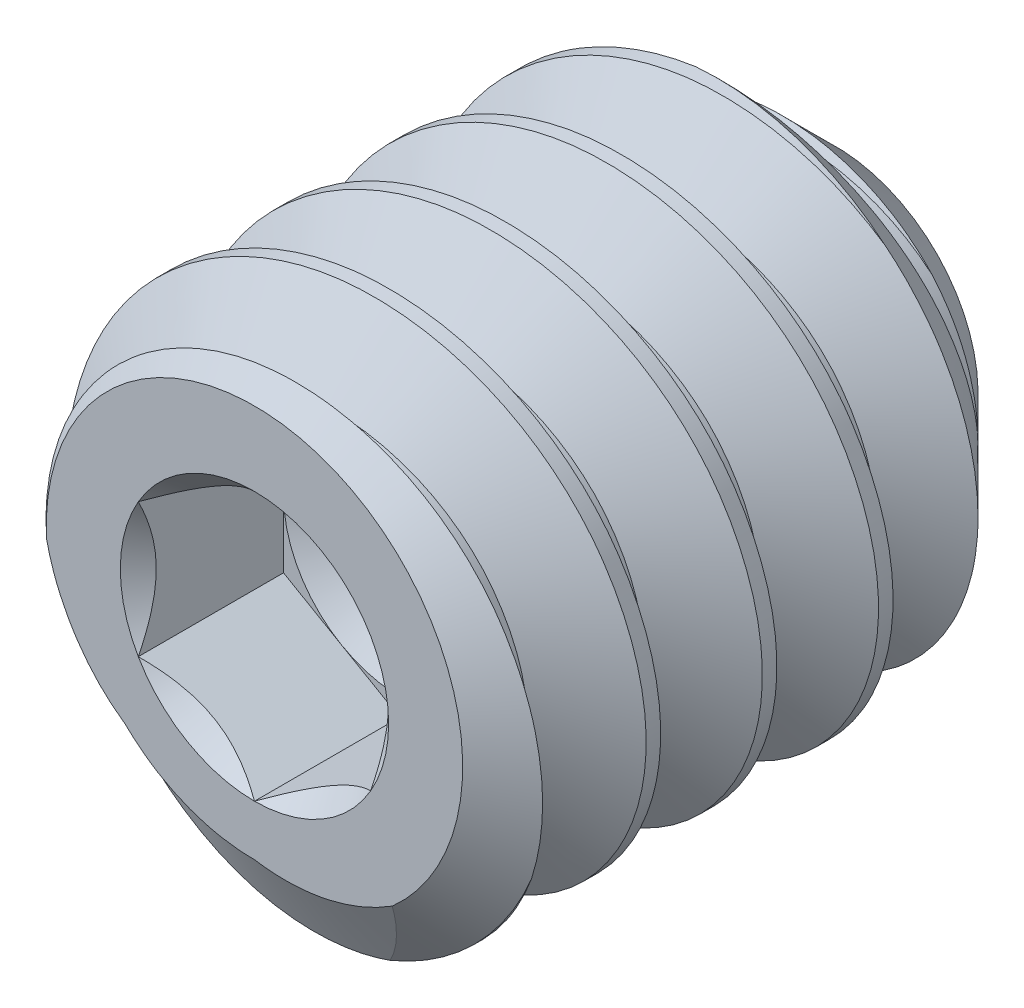
SolidWorks part; units mm, degrees
ref_plane "Front" through (0, 0, 0) normal (0, 0, 1) x (1, 0, 0)
ref_plane "Top" through (0, 0, 0) normal (0, 1, 0) x (1, 0, 0)
ref_plane "Right" through (0, 0, 0) normal (1, 0, 0) x (0, 0, -1)
sketch "Sketch22" plane through (0, 0, 0) normal (1, 0, 0) x (0, 0, -1)
  line L0 (-1.3533, 0) -> (-1.3533, 1.1379)
  line L1 (-1.3533, 1.1379) -> (-1.1541, 1.4224)
  line L2 (-1.1541, 1.4224) -> (1.1787, 1.4224)
  line L3 (1.1787, 1.4224) -> (1.8217, 0.7794)
  line L4 (1.8217, 0.7794) -> (1.3533, 0) construction
  line L5 (1.3533, 0) -> (-1.3533, 0)
  line L6 (1.3533, 0) -> (1.8217, 0) construction
  line L7 (1.8217, 0) -> (1.8217, 0.7794) construction
  line L8 (1.8217, -0.7794) -> (1.3533, 0) construction
  line L9 (-1.1541, -1.4224) -> (1.1787, -1.4224) construction
  line L10 (1.8217, 0.7794) -> (1.8217, 0)
  line L11 (1.8217, 0) -> (1.3533, 0)
  dimension "Dia" = 2.8448
  dimension "Length" = 3.175
  dimension "D3" = 35
  dimension "D5" = 118
  dimension "D6" = 45
  dimension "D7" = 2.2758
revolve "Revolve1" add sketch "Sketch22" angle 360 about L6
ref_plane "Plane1" through (0, 0, -1.8217) normal (0, 0, 1) x (1, 0, 0)
sketch "Sketch27" plane through (0, 0, -1.8217) normal (0, 0, 1) x (1, 0, 0)
  circle A0 centre (0, 0) radius 1.4224 construction
  circle A1 centre (0, 0) radius 1.4224
curve "Helix/Spiral1" pitch 0.635 height 3.81 radius 1.4224 centre (0, 0, -1.8217) axis (0, 0, 1) start towards (0, 1, 0)
sketch "Sketch28" plane through (0, 0, 0) normal (1, 0, 0) x (0, 0, -1)
  line L0 (1.8217, 1.4224) -> (2.3773, 1.4224)
  line L1 (2.3773, 1.4224) -> (2.1392, 1.01)
  line L2 (2.1392, 1.01) -> (2.0598, 1.01)
  line L3 (2.0598, 1.01) -> (1.8217, 1.4224)
  line L4 (1.9407, 1.2162) -> (2.2582, 1.2162) construction
  line L6 (-1.1541, 1.4224) -> (1.1787, 1.4224) construction
  line L7 (1.8217, 6.985) -> (1.8217, -6.985) construction
  dimension "D1" = 0.0794
  dimension "D2" = 0.3175
  dimension "D3" = 60
sweep "Cut-Sweep2" cut profiles "Sketch28" path "Helix/Spiral1" align with end faces yes
sketch "Sketch23" plane through (0, 0, 1.3533) normal (0, 0, 1) x (1, 0, 0)
  line L1 (0, 0.7332) -> (-0.635, 0.3666)
  line L2 (-0.635, 0.3666) -> (-0.635, -0.3666)
  line L3 (-0.635, -0.3666) -> (0, -0.7332)
  line L4 (0, -0.7332) -> (0.635, -0.3666)
  line L5 (0.635, -0.3666) -> (0.635, 0.3666)
  line L6 (0.635, 0.3666) -> (0, 0.7332)
  circle A0 centre (0, 0) radius 0.635 construction
  dimension "Hex" = 1.27
extrude "Cut-Extrude10" cut sketch "Sketch23" against normal blind 0.7937
sketch "Sketch24" plane through (0, 0, 1.3533) normal (0, 0, 1) x (1, 0, 0)
  circle A0 centre (0, 0) radius 0.7332
extrude "Cut-Extrude11" cut sketch "Sketch24" against normal through all draft 45
sketch "Sketch26" plane through (0, 0, 0.5596) normal (0, 0, 1) x (1, 0, 0)
  circle A0 centre (0, 0) radius 0.635 construction
  circle A1 centre (0, 0) radius 0.635
extrude "Cut-Extrude12" cut sketch "Sketch26" against normal through all draft 60
sketch "Sketch30" plane through (0, 0, 0) normal (1, 0, 0) x (0, 0, -1)
  line L0 (-1.1541, 1.4224) -> (1.1787, 1.4224) construction
  line L1 (-1.3533, 0) -> (-1.3533, 1.1379) construction
  line L2 (1.8217, 0) -> (1.8217, 0.7794) construction
  line L3 (-1.1541, -1.4224) -> (1.1787, -1.4224) construction
  point P0 (-1.3533, 1.4224)
  point P1 (1.8217, 1.4224)
  point P2 (1.8217, -1.4224)
  point P11 (-0.4008, -1.4224)
  dimension "D1" = 2.2225
sketch "Sketch31" plane through (0, 0, 0) normal (1, 0, 0) x (0, 0, -1)
  line L2 (1.3533, 0) -> (1.8217, -0.7794)
  line L3 (1.8217, 0.7794) -> (1.3533, 0)
equation "\"D7@Sketch22\"=\"Dia@Sketch22\"*.8"
equation "\"D1@Sketch28\" = \"D4@Helix/Spiral1\" * .125"
equation "\"D3@Helix/Spiral1\" = \"Length@Sketch22\" + \"D4@Helix/Spiral1\""
equation "\"D1@Sketch30\" = \"D4@Helix/Spiral1\" * 3.5"
equation "\"hex Depth@Cut-Extrude10\" = \"Hex@Sketch23\" * .625"
equation "\"D2@Sketch28\" = \"D4@Helix/Spiral1\" * .5"
